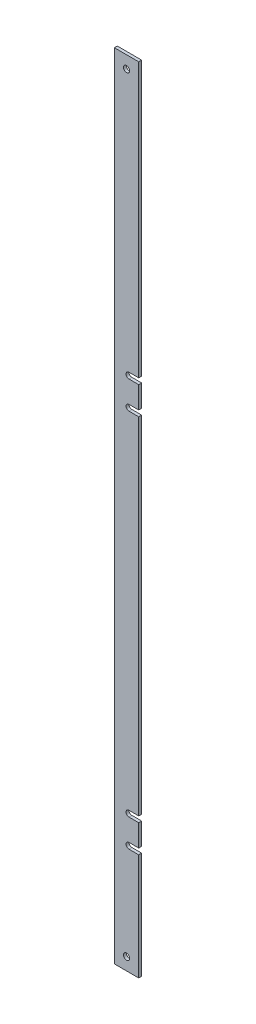
SolidWorks part; units mm, degrees
ref_plane "Front Plane" through (0, 0, 0) normal (0, 0, 1) x (1, 0, 0)
ref_plane "Top Plane" through (0, 0, 0) normal (0, 1, 0) x (1, 0, 0)
ref_plane "Right Plane" through (0, 0, 0) normal (1, 0, 0) x (0, 0, -1)
sketch "Sketch1" plane through (0, 0, 0) normal (0, 0, 1) x (1, 0, 0)
  line L15 (-12.5, 406.4) -> (12.5, 406.4)
  line L24 (-12.5, 406.4) -> (-12.5, -406.4)
  line L27 (-12.5, -406.4) -> (12.5, -406.4)
  line L30 (12.5, 406.4) -> (12.5, -406.4)
  line L40 (-12.5, 406.4) -> (12.5, -406.4) construction
  line L41 (-12.5, -406.4) -> (12.5, 406.4) construction
  point P0 (0, 0)
  dimension "D2" = 25
  dimension "D1" = 812.8
extrude "Boss-Extrude1" add sketch "Sketch1" along normal blind 3 contours L24 L15 L30 L27
sketch "Sketch5" plane through (0, 0, 3) normal (0, 0, 1) x (1, 0, 0)
  line L0 (2.5, 122.9801) -> (22.5, 122.9801) construction
  line L1 (2.5, 125.9801) -> (22.5, 125.9801)
  line L2 (2.5, 119.9801) -> (22.5, 119.9801)
  line L3 (12.5, 406.4) -> (12.5, -406.4) construction
  line L4 (2.5, 94.4801) -> (22.5, 94.4801) construction
  line L5 (2.5, 97.4801) -> (22.5, 97.4801)
  line L6 (2.5, 91.4801) -> (22.5, 91.4801)
  line L7 (2.5, -265.6299) -> (22.5, -265.6299) construction
  line L8 (2.5, -262.6299) -> (22.5, -262.6299)
  line L11 (2.5, -268.6299) -> (22.5, -268.6299)
  line L14 (2.5, -294.1299) -> (22.5, -294.1299) construction
  line L15 (2.5, -291.1299) -> (22.5, -291.1299)
  line L16 (2.5, -297.1299) -> (22.5, -297.1299)
  arc A0 (2.5, 125.9801) -> (2.5, 119.9801) centre (2.5, 122.9801) ccw
  arc A1 (22.5, 119.9801) -> (22.5, 125.9801) centre (22.5, 122.9801) ccw
  arc A2 (2.5, 97.4801) -> (2.5, 91.4801) centre (2.5, 94.4801) ccw
  arc A3 (22.5, 91.4801) -> (22.5, 97.4801) centre (22.5, 94.4801) ccw
  circle A12 centre (5.5, 122.9801) radius 2.6585 construction
  circle A13 centre (5.5, 122.9801) radius 2.6585 construction
  circle A14 centre (5.5, -265.6299) radius 2.6585 construction
  arc A15 (2.5, -262.6299) -> (2.5, -268.6299) centre (2.5, -265.6299) ccw
  arc A16 (22.5, -268.6299) -> (22.5, -262.6299) centre (22.5, -265.6299) ccw
  arc A17 (2.5, -291.1299) -> (2.5, -297.1299) centre (2.5, -294.1299) ccw
  arc A18 (22.5, -297.1299) -> (22.5, -291.1299) centre (22.5, -294.1299) ccw
  point P2 (12.5, 122.9801)
  point P7 (-0.5, 122.9801)
  point P14 (12.5, 94.4801)
  point P22 (12.5, -265.6299)
  point P29 (12.5, -294.1299)
  dimension "D1" = 13
  dimension "D2" = 6
  dimension "D3" = 2
  dimension "D4" = 2
extrude "Cut-Extrude4" cut sketch "Sketch5" against normal blind 10
hole_wizard "1/4 (0.25) Diameter Hole1" positions "Sketch6" profile "Sketch7" hole size "1/4" standard "ANSI Inch"
sketch "Sketch6" plane through (0, 0, 3) normal (0, 0, 1) x (1, 0, 0)
  line L0 (-12.5, 406.4) -> (12.5, 406.4) construction
  line L1 (0, 0) -> (-12.5, 0) construction
  line L2 (-12.5, 406.4) -> (-12.5, -406.4) construction
  point P0 (0, 393.7)
  point P12 (0, 0)
  point P13 (0, 0)
  point P14 (0, -393.7)
  dimension "D1" = 12.7
sketch "Sketch7" plane through (0, 393.7, 3) normal (1, 0, 0) x (0, -1, 0)
  line L0 (0, 0) -> (0, 7.7477)
  line L1 (0, 7.7477) -> (3.175, 5.84)
  line L2 (3.175, 5.84) -> (3.175, 0)
  line L5 (3.175, 0) -> (0, 0)
  line L10 (0, 7.7477) -> (-3.175, 5.84) construction
  line L11 (0, -6.35) -> (0, 107.95) construction
  dimension "Hole Dia." = 6.35
  dimension "Hole Depth" = 5.84
  dimension "Drill Angle" = 118
